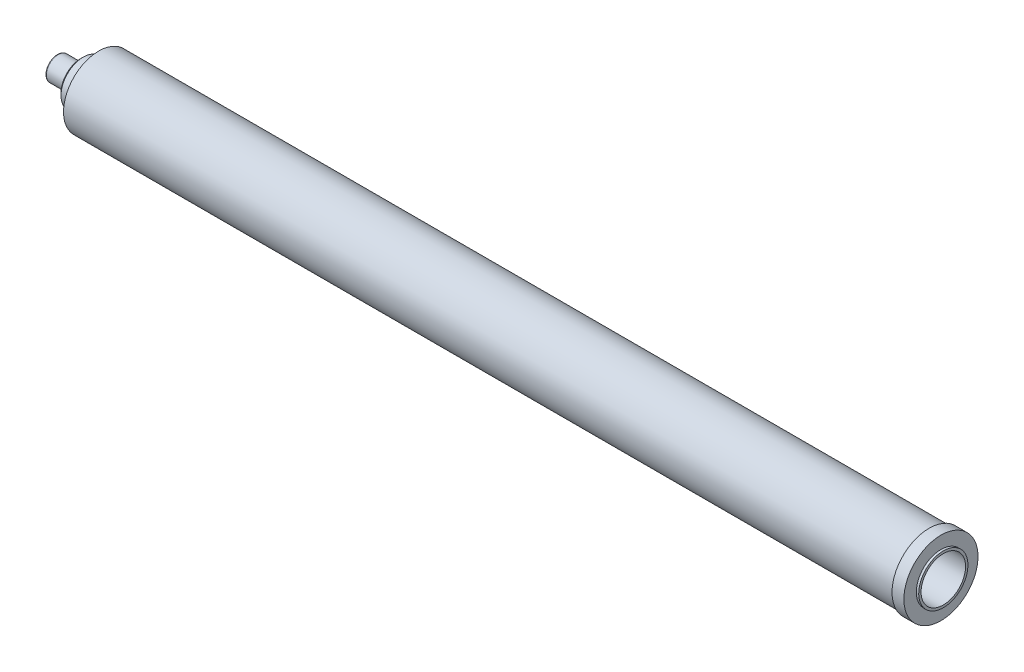
SolidWorks part; units mm, degrees
material "6061 Alloy"
ref_plane "Front Plane" through (0, 0, 0) normal (0, 0, 1) x (1, 0, 0)
ref_plane "Top Plane" through (0, 0, 0) normal (0, 1, 0) x (1, 0, 0)
ref_plane "Right Plane" through (0, 0, 0) normal (1, 0, 0) x (0, 0, -1)
sketch "Sketch1" plane through (0, 0, 0) normal (0, 0, 1) x (1, 0, 0)
  line L0 (0, 0) -> (0, 12.7)
  line L1 (0, 12.7) -> (25.4, 12.7)
  line L2 (25.4, 12.7) -> (25.4, 23.8125)
  line L3 (25.4, 23.8125) -> (44.45, 23.8125)
  line L4 (44.45, 23.8125) -> (44.45, 37.6555)
  line L5 (44.45, 37.6555) -> (933.45, 37.6555)
  line L6 (933.45, 37.6555) -> (933.45, 39.6875)
  line L7 (933.45, 39.6875) -> (946.15, 39.6875)
  line L8 (946.15, 39.6875) -> (946.15, 0)
  line L9 (946.15, 0) -> (0, 0)
  dimension "D1" = 25.4
  dimension "D2" = 23.8125
  dimension "D3" = 12.7
  dimension "D4" = 44.45
  dimension "D5" = 889
  dimension "D6" = 12.7
  dimension "D7" = 39.6875
  dimension "D8" = 37.6555
revolve "Revolve1" add sketch "Sketch1" angle 360 about L9
chamfer "Chamfer1" distance 2.54 angle 45 1 edges at (25.4, 23.8125, 0)
hole_wizard "CSK for 3/8 Flat Head Machine Screw (100)1" positions "Sketch3" profile "Sketch4" countersink size "3/8" standard "ANSI Inch"
sketch "Sketch3" plane through (0, 0, 0) normal (-1, 0, 0) x (0, 0, 1)
  point P0 (0, 0)
sketch "Sketch4" plane through (0, 0, 0) normal (0, 1, 0) x (0, 0, 1)
  line L0 (0, 0) -> (0, 28.4295)
  line L1 (0, 28.4295) -> (5.0419, 25.4)
  line L2 (5.0419, 25.4) -> (5.0419, 3.8896)
  line L3 (5.0419, 3.8896) -> (9.6774, 0)
  line L5 (9.6774, 0) -> (0, 0)
  line L6 (-5.0419, 3.8896) -> (-9.6774, 0) construction
  line L10 (0, 28.4295) -> (-5.0419, 25.4) construction
  line L11 (0, -6.35) -> (0, 107.95) construction
  dimension "Hole Dia." = 10.0838
  dimension "Hole Depth" = 25.4
  dimension "Near C'Sink Dia." = 19.3548
  dimension "Near C'Sink Angle" = 100
  dimension "Drill Angle" = 118
fillet "Fillet2" radius 1.27 1 edges at (0, 12.7, 0)
sketch "Sketch5" plane through (946.15, 0, 0) normal (1, 0, 0) x (0, 0, -1)
  circle A0 centre (0, 0) radius 23.8125
  circle A1 centre (0, 0) radius 26.3525
  dimension "D1" = 47.625
  dimension "D2" = 2.54
extrude "Boss-Extrude1" add sketch "Sketch5" along normal blind 2.54
sketch "Sketch6" plane through (948.69, 0, 0) normal (1, 0, 0) x (0, 0, -1)
  circle A0 centre (0, 0) radius 23.8125
extrude "Cut-Extrude1" cut sketch "Sketch6" against normal blind 508
